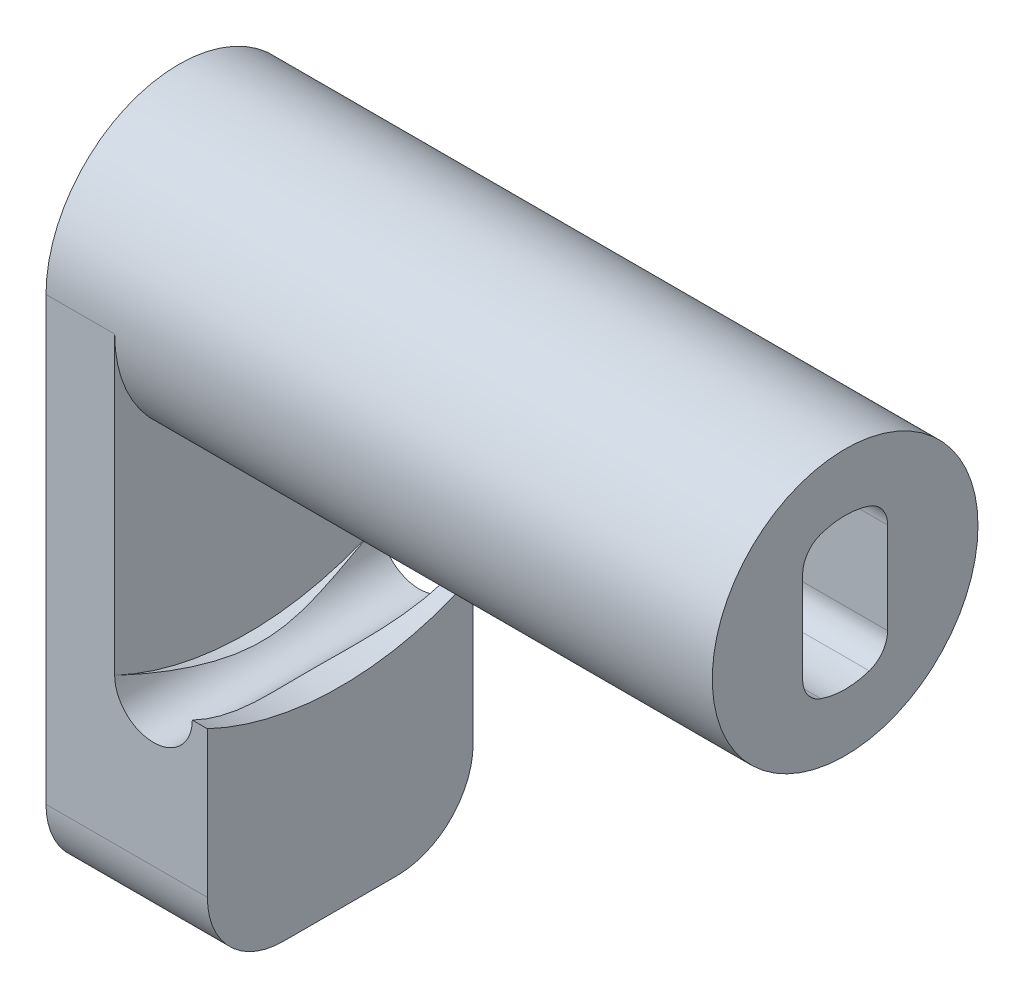
SolidWorks part; units mm, degrees
material "ABS"
ref_plane "Front Plane" through (0, 0, 0) normal (1, 0, 0) x (0, 1, 0)
ref_plane "Top Plane" through (0, 0, 0) normal (0, 0, 1) x (0, 1, 0)
ref_plane "Right Plane" through (0, 0, 0) normal (0, 1, 0) x (-1, 0, 0)
sketch "Sketch1" plane through (0, 0, 0) normal (1, 0, 0) x (0, 1, 0)
  circle A2 centre (0, 0) radius 8.7376
  dimension "D3" = 17.4752
extrude "Boss-Extrude1" add sketch "Sketch1" along normal blind 43.815 contours A2 region at (0, 0, 0)
sketch "Sketch10" plane through (0, 0, 0) normal (-1, 0, 0) x (0, -1, 0)
  line L0 (0, 8.7376) -> (34.036, 8.7376)
  line L2 (34.036, 8.7376) -> (34.036, -8.7376)
  line L3 (34.036, -8.7376) -> (0, -8.7376)
  circle A0 centre (0, 0) radius 8.7376 construction
  arc A2 (0, 8.7376) -> (0, -8.7376) centre (0, 0) cw
  dimension "D1" = 34.036
extrude "Boss-Extrude3" add sketch "Sketch10" against normal blind 4.516 contours L0 A2 L3 L2 region at (0, -20.3793, 0)
fillet "Fillet2" radius 5 2 edges at (2.258, -34.036, 8.7376) (2.258, -34.036, -8.7376)
sketch "Sketch14" [suppressed] plane through (0, 0, 0) normal (-1, 0, 0) x (0, 0, 1)
  line L0 (0.5115, -3.4237) -> (0.3944, -4.0089)
  line L1 (0, 0) -> (0, -4.064) construction
  line L2 (0, 0) -> (0.5606, -3.4335) construction
  line L3 (0.6039, -3.4087) -> (0.9011, -3.9262)
  line L4 (-0.6903, -3.3922) -> (-1.0005, -3.9021)
  line L5 (-0.5983, -3.4096) -> (-0.4961, -3.9976)
  line L6 (-1.8089, -2.9515) -> (-2.2748, -3.3245)
  line L7 (-1.7284, -2.9994) -> (-1.8334, -3.5869)
  line L8 (-2.7093, -2.1549) -> (-3.2746, -2.346)
  line L9 (-2.65, -2.2273) -> (-2.9496, -2.7435)
  line L10 (-3.2829, -1.0983) -> (-3.8795, -1.0846)
  line L11 (-3.252, -1.1867) -> (-3.7101, -1.5692)
  line L12 (-3.4605, 0.0907) -> (-4.0165, 0.3077)
  line L13 (-3.4617, -0.0029) -> (-4.023, -0.2057)
  line L14 (-3.2208, 1.2689) -> (-3.669, 1.6629)
  line L15 (-3.2539, 1.1813) -> (-3.8507, 1.1827)
  line L16 (-2.5926, 2.2939) -> (-2.879, 2.8175)
  line L17 (-2.6537, 2.223) -> (-3.214, 2.4284)
  line L18 (-1.6517, 3.0423) -> (-1.7417, 3.6323)
  line L19 (-1.7333, 2.9965) -> (-2.1896, 3.3812)
  line L20 (-0.5115, 3.4237) -> (-0.3944, 4.0089)
  line L21 (-0.6039, 3.4087) -> (-0.9011, 3.9262)
  line L22 (0.6903, 3.3922) -> (1.0005, 3.9021)
  line L23 (0.5983, 3.4096) -> (0.4961, 3.9976)
  line L24 (1.8089, 2.9515) -> (2.2748, 3.3245)
  line L25 (1.7284, 2.9994) -> (1.8334, 3.5869)
  line L26 (2.7093, 2.1549) -> (3.2746, 2.346)
  line L27 (2.65, 2.2273) -> (2.9496, 2.7435)
  line L28 (3.2829, 1.0983) -> (3.8795, 1.0846)
  line L29 (3.252, 1.1867) -> (3.7101, 1.5692)
  line L30 (3.4605, -0.0907) -> (4.0165, -0.3077)
  line L31 (3.4617, 0.0029) -> (4.023, 0.2057)
  line L32 (3.2208, -1.2689) -> (3.669, -1.6629)
  line L33 (3.2539, -1.1813) -> (3.8507, -1.1827)
  line L34 (2.5926, -2.2939) -> (2.879, -2.8175)
  line L35 (2.6537, -2.223) -> (3.214, -2.4284)
  line L36 (1.6517, -3.0423) -> (1.7417, -3.6323)
  line L37 (1.7333, -2.9965) -> (2.1896, -3.3812)
  line L38 (-0.1032, -4.0627) -> (0, -4.064)
  line L39 (-1.4865, -3.7824) -> (-1.39, -3.8189)
  line L40 (-2.6905, -3.0459) -> (-2.6123, -3.1132)
  line L41 (-3.5195, -2.032) -> (-3.57, -1.942)
  line L42 (-4.0023, -0.7057) -> (-4.0189, -0.6039)
  line L43 (-4.0023, 0.7057) -> (-3.9831, 0.8071)
  line L44 (-3.5195, 2.032) -> (-3.4668, 2.1207)
  line L45 (-2.6123, 3.1132) -> (-2.5324, 3.1785)
  line L46 (-1.39, 3.8189) -> (-1.2926, 3.853)
  line L47 (0, 4.064) -> (0.1032, 4.0627)
  line L48 (1.39, 3.8189) -> (1.4865, 3.7824)
  line L49 (2.6123, 3.1132) -> (2.6905, 3.0459)
  line L50 (3.5195, 2.032) -> (3.57, 1.942)
  line L51 (4.0023, 0.7057) -> (4.0189, 0.6039)
  line L52 (4.0023, -0.7057) -> (3.9831, -0.8071)
  line L53 (3.5195, -2.032) -> (3.4668, -2.1207)
  line L54 (2.6123, -3.1132) -> (2.5324, -3.1785)
  line L55 (1.39, -3.8189) -> (1.2926, -3.853)
  arc A0 (0.3497, -4.0489) -> (0, -4.064) centre (0, 0) cw
  arc A1 (0.3497, -4.0489) -> (0.3944, -4.0089) centre (0.3454, -3.9991) ccw
  arc A2 (0.5115, -3.4237) -> (0.6039, -3.4087) centre (0.5606, -3.4335) cw
  arc A3 (0.4203, -4.0631) -> (0.3944, -4.0089) centre (0.4434, -4.0187) cw
  arc A4 (0.4203, -4.0631) -> (0.7372, -4.2116) centre (2.3016, -0.4608) ccw
  arc A6 (0.9562, -3.9499) -> (0.9011, -3.9262) centre (0.9445, -3.9013) cw
  arc A7 (0.9562, -3.9499) -> (1.2926, -3.853) centre (0, 0) ccw
  arc A8 (-1.0562, -3.9243) -> (-1.39, -3.8189) centre (0, 0) cw
  arc A9 (-1.0562, -3.9243) -> (-1.0005, -3.9021) centre (-1.0432, -3.8761) ccw
  arc A10 (-0.6903, -3.3922) -> (-0.5983, -3.4096) centre (-0.6476, -3.4182) cw
  arc A11 (-0.4524, -4.0387) -> (-0.4961, -3.9976) centre (-0.4468, -3.9891) cw
  arc A12 (-0.4524, -4.0387) -> (-0.1032, -4.0627) centre (0, 0) ccw
  arc A13 (-2.3347, -3.3264) -> (-2.6123, -3.1132) centre (0, 0) cw
  arc A14 (-2.3347, -3.3264) -> (-2.2748, -3.3245) centre (-2.306, -3.2855) ccw
  arc A15 (-1.8089, -2.9515) -> (-1.7284, -2.9994) centre (-1.7776, -2.9906) cw
  arc A16 (-1.8064, -3.6405) -> (-1.8334, -3.5869) centre (-1.7842, -3.5957) cw
  arc A17 (-1.8064, -3.6405) -> (-1.4865, -3.7824) centre (0, 0) ccw
  arc A18 (-3.3316, -2.3273) -> (-3.5195, -2.032) centre (0, 0) cw
  arc A19 (-3.3316, -2.3273) -> (-3.2746, -2.346) centre (-3.2906, -2.2987) ccw
  arc A20 (-2.7093, -2.1549) -> (-2.65, -2.2273) centre (-2.6933, -2.2022) cw
  arc A21 (-2.9426, -2.8031) -> (-2.9496, -2.7435) centre (-2.9064, -2.7686) cw
  arc A22 (-2.9426, -2.8031) -> (-2.6905, -3.0459) centre (0, 0) ccw
  arc A23 (-3.9267, -1.0475) -> (-4.0023, -0.7057) centre (0, 0) cw
  arc A24 (-3.9267, -1.0475) -> (-3.8795, -1.0846) centre (-3.8784, -1.0346) ccw
  arc A25 (-3.2829, -1.0983) -> (-3.252, -1.1867) centre (-3.284, -1.1483) cw
  arc A26 (-3.7238, -1.6276) -> (-3.7101, -1.5692) centre (-3.678, -1.6076) cw
  arc A27 (-3.7238, -1.6276) -> (-3.57, -1.942) centre (0, 0) ccw
  arc A28 (-4.0481, 0.3587) -> (-4.0023, 0.7057) centre (0, 0) cw
  arc A29 (-4.0481, 0.3587) -> (-4.0165, 0.3077) centre (-3.9983, 0.3543) ccw
  arc A30 (-3.4605, 0.0907) -> (-3.4617, -0.0029) centre (-3.4787, 0.0442) cw
  arc A31 (-4.0559, -0.2558) -> (-4.023, -0.2057) centre (-4.006, -0.2527) cw
  arc A32 (-4.0559, -0.2558) -> (-4.0189, -0.6039) centre (0, 0) ccw
  arc A33 (-3.6813, 1.7216) -> (-3.5195, 2.032) centre (0, 0) cw
  arc A34 (-3.6813, 1.7216) -> (-3.669, 1.6629) centre (-3.636, 1.7005) ccw
  arc A35 (-3.2208, 1.2689) -> (-3.2539, 1.1813) centre (-3.2538, 1.2313) cw
  arc A36 (-3.8988, 1.1468) -> (-3.8507, 1.1827) centre (-3.8509, 1.1327) cw
  arc A37 (-3.8988, 1.1468) -> (-3.9831, 0.8071) centre (0, 0) ccw
  arc A38 (-2.8705, 2.8769) -> (-2.6123, 3.1132) centre (0, 0) cw
  arc A39 (-2.8705, 2.8769) -> (-2.879, 2.8175) centre (-2.8352, 2.8415) ccw
  arc A40 (-2.5926, 2.2939) -> (-2.6537, 2.223) centre (-2.6365, 2.2699) cw
  arc A41 (-3.2715, 2.4111) -> (-3.214, 2.4284) centre (-3.2312, 2.3815) cw
  arc A42 (-3.2715, 2.4111) -> (-3.4668, 2.1207) centre (0, 0) ccw
  arc A43 (-1.7134, 3.6852) -> (-1.39, 3.8189) centre (0, 0) cw
  arc A44 (-1.7134, 3.6852) -> (-1.7417, 3.6323) centre (-1.6923, 3.6398) ccw
  arc A45 (-1.6517, 3.0423) -> (-1.7333, 2.9965) centre (-1.7011, 3.0348) cw
  arc A46 (-2.2495, 3.3846) -> (-2.1896, 3.3812) centre (-2.2218, 3.343) cw
  arc A47 (-2.2495, 3.3846) -> (-2.5324, 3.1785) centre (0, 0) ccw
  arc A48 (-0.3497, 4.0489) -> (0, 4.064) centre (0, 0) cw
  arc A49 (-0.3497, 4.0489) -> (-0.3944, 4.0089) centre (-0.3454, 3.9991) ccw
  arc A50 (-0.5115, 3.4237) -> (-0.6039, 3.4087) centre (-0.5606, 3.4335) cw
  arc A51 (-0.9562, 3.9499) -> (-0.9011, 3.9262) centre (-0.9445, 3.9013) cw
  arc A52 (-0.9562, 3.9499) -> (-1.2926, 3.853) centre (0, 0) ccw
  arc A53 (1.0562, 3.9243) -> (1.39, 3.8189) centre (0, 0) cw
  arc A54 (1.0562, 3.9243) -> (1.0005, 3.9021) centre (1.0432, 3.8761) ccw
  arc A55 (0.6903, 3.3922) -> (0.5983, 3.4096) centre (0.6476, 3.4182) cw
  arc A56 (0.4524, 4.0387) -> (0.4961, 3.9976) centre (0.4468, 3.9891) cw
  arc A57 (0.4524, 4.0387) -> (0.1032, 4.0627) centre (0, 0) ccw
  arc A58 (2.3347, 3.3264) -> (2.6123, 3.1132) centre (0, 0) cw
  arc A59 (2.3347, 3.3264) -> (2.2748, 3.3245) centre (2.306, 3.2855) ccw
  arc A60 (1.8089, 2.9515) -> (1.7284, 2.9994) centre (1.7776, 2.9906) cw
  arc A61 (1.8064, 3.6405) -> (1.8334, 3.5869) centre (1.7842, 3.5957) cw
  arc A62 (1.8064, 3.6405) -> (1.4865, 3.7824) centre (0, 0) ccw
  arc A63 (3.3316, 2.3273) -> (3.5195, 2.032) centre (0, 0) cw
  arc A64 (3.3316, 2.3273) -> (3.2746, 2.346) centre (3.2906, 2.2987) ccw
  arc A65 (2.7093, 2.1549) -> (2.65, 2.2273) centre (2.6933, 2.2022) cw
  arc A66 (2.9426, 2.8031) -> (2.9496, 2.7435) centre (2.9064, 2.7686) cw
  arc A67 (2.9426, 2.8031) -> (2.6905, 3.0459) centre (0, 0) ccw
  arc A68 (3.9267, 1.0475) -> (4.0023, 0.7057) centre (0, 0) cw
  arc A69 (3.9267, 1.0475) -> (3.8795, 1.0846) centre (3.8784, 1.0346) ccw
  arc A70 (3.2829, 1.0983) -> (3.252, 1.1867) centre (3.284, 1.1483) cw
  arc A71 (3.7238, 1.6276) -> (3.7101, 1.5692) centre (3.678, 1.6076) cw
  arc A72 (3.7238, 1.6276) -> (3.57, 1.942) centre (0, 0) ccw
  arc A73 (4.0481, -0.3587) -> (4.0023, -0.7057) centre (0, 0) cw
  arc A74 (4.0481, -0.3587) -> (4.0165, -0.3077) centre (3.9983, -0.3543) ccw
  arc A75 (3.4605, -0.0907) -> (3.4617, 0.0029) centre (3.4787, -0.0442) cw
  arc A76 (4.0559, 0.2558) -> (4.023, 0.2057) centre (4.006, 0.2527) cw
  arc A77 (4.0559, 0.2558) -> (4.0189, 0.6039) centre (0, 0) ccw
  arc A78 (3.6813, -1.7216) -> (3.5195, -2.032) centre (0, 0) cw
  arc A79 (3.6813, -1.7216) -> (3.669, -1.6629) centre (3.636, -1.7005) ccw
  arc A80 (3.2208, -1.2689) -> (3.2539, -1.1813) centre (3.2538, -1.2313) cw
  arc A81 (3.8988, -1.1468) -> (3.8507, -1.1827) centre (3.8509, -1.1327) cw
  arc A82 (3.8988, -1.1468) -> (3.9831, -0.8071) centre (0, 0) ccw
  arc A83 (2.8705, -2.8769) -> (2.6123, -3.1132) centre (0, 0) cw
  arc A84 (2.8705, -2.8769) -> (2.879, -2.8175) centre (2.8352, -2.8415) ccw
  arc A85 (2.5926, -2.2939) -> (2.6537, -2.223) centre (2.6365, -2.2699) cw
  arc A86 (3.2715, -2.4111) -> (3.214, -2.4284) centre (3.2312, -2.3815) cw
  arc A87 (3.2715, -2.4111) -> (3.4668, -2.1207) centre (0, 0) ccw
  arc A88 (1.7134, -3.6852) -> (1.39, -3.8189) centre (0, 0) cw
  arc A89 (1.7134, -3.6852) -> (1.7417, -3.6323) centre (1.6923, -3.6398) ccw
  arc A90 (1.6517, -3.0423) -> (1.7333, -2.9965) centre (1.7011, -3.0348) cw
  arc A91 (2.2495, -3.3846) -> (2.1896, -3.3812) centre (2.2218, -3.343) cw
  arc A92 (2.2495, -3.3846) -> (2.5324, -3.1785) centre (0, 0) ccw
  point P207 (0, 0)
  dimension "D1" = 4.064
  dimension "D2" = 0.05
  dimension "D3" = 0.05
  dimension "D4" = 0.04
  dimension "D5" = 18
  dimension "D6" = 0.5968
  dimension "D8" = 0.35
sketch "Sketch15" plane through (4.516, 0, 0) normal (1, 0, 0) x (0, 1, 0)
  line L1 (-29.036, 8.7376) -> (-18.796, 8.7376)
  line L2 (-18.796, 8.7376) -> (-18.796, -8.7376)
  line L3 (0, 8.7376) -> (-29.036, 8.7376) construction
  line L4 (-29.036, -8.7376) -> (-18.796, -8.7376)
  line L5 (-34.036, 3.7376) -> (-34.036, -3.7376) construction
  line L6 (-34.036, 3.7376) -> (-34.036, -3.7376)
  line L8 (-29.036, -8.7376) -> (0, -8.7376) construction
  line L13 (0, 8.7376) -> (-29.036, 8.7376)
  line L14 (-34.036, 3.7376) -> (-34.036, -3.7376)
  line L15 (-29.036, -8.7376) -> (0, -8.7376)
  line L17 (-34.036, 3.7376) -> (-34.036, -3.7376)
  arc A0 (-29.036, 8.7376) -> (-34.036, 3.7376) centre (-29.036, 3.7376) ccw construction
  arc A1 (-34.036, -3.7376) -> (-29.036, -8.7376) centre (-29.036, -3.7376) ccw construction
  arc A2 (-29.036, 8.7376) -> (-34.036, 3.7376) centre (-29.036, 3.7376) ccw
  arc A3 (-34.036, -3.7376) -> (-29.036, -8.7376) centre (-29.036, -3.7376) ccw
  arc A7 (-29.036, 8.7376) -> (-34.036, 3.7376) centre (-29.036, 3.7376) ccw
  arc A8 (-34.036, -3.7376) -> (-29.036, -8.7376) centre (-29.036, -3.7376) ccw
  arc A9 (0, 8.7376) -> (0, -8.7376) centre (0, 0) ccw
  arc A10 (-29.036, 8.7376) -> (-34.036, 3.7376) centre (-29.036, 3.7376) ccw
  arc A11 (-34.036, -3.7376) -> (-29.036, -8.7376) centre (-29.036, -3.7376) ccw
  arc A12 (0, 8.7376) -> (0, -8.7376) centre (0, 0) ccw
  line M2 (0, 8.7376) -> (-29.036, 8.7376)
  arc M3 (-29.036, 8.7376) -> (-34.036, 3.7376) centre (-29.036, 3.7376) ccw
  line M4 (-34.036, 3.7376) -> (-34.036, -3.7376)
  arc M5 (-34.036, -3.7376) -> (-29.036, -8.7376) centre (-29.036, -3.7376) ccw
  dimension "D1" = 15.24
  dimension "D2" = 0
extrude "Boss-Extrude4" add sketch "Sketch15" along normal blind 6.096 contours M2 M3 M4 M5 region at (4.516, -26.143, 0)
sketch "Sketch21" plane through (10.612, 0, 0) normal (1, 0, 0) x (0, 1, 0)
  line L2 (-18.796, -8.7376) -> (-18.796, 8.7376)
  line L4 (-29.036, 8.7376) -> (-18.796, 8.7376) construction
  line L5 (-19.431, -8.7376) -> (-18.796, -8.7376)
  line L6 (-18.796, 8.7376) -> (-18.796, -8.7376) construction
  line L8 (-18.796, -8.7376) -> (0, -8.7376) construction
  line L14 (-18.796, -8.7376) -> (-18.796, 8.7376) construction
  line L20 (-18.796, 8.7376) -> (-29.036, 8.7376)
  arc A2 (-19.431, -8.7376) -> (-19.431, 8.7376) centre (-1.0855, 0) cw
  dimension "D4" = 20.32
  dimension "D2" = 0.635
  dimension "D3" = 0.635
extrude "Cut-Extrude8" cut sketch "Sketch21" against normal up to surface (6.096 mm away) contours A2 L2 region at (10.612, -19.8652, 0) up to face at (4.516, -11.5824, 0)
sketch "Sketch22" plane through (43.815, 0, 0) normal (1, 0, 0) x (0, 1, 0)
  line L7 (-4.0897, -2.794) -> (4.0897, 2.794) construction
  line L8 (-4.0897, 2.794) -> (4.0897, -2.794) construction
  line L11 (-4.0897, -2.794) -> (4.0897, -2.794)
  line L13 (-4.0897, 2.794) -> (4.0897, 2.794)
  line L15 (-4.0897, -2.794) -> (4.0897, 2.794) construction
  line L16 (-4.0897, 2.794) -> (4.0897, -2.794) construction
  arc A3 (-4.0897, 2.794) -> (-4.0897, -2.794) centre (0, 0) ccw
  arc A4 (4.0897, -2.794) -> (4.0897, 2.794) centre (0, 0) ccw
  dimension "D2" = 9.906
  dimension "D3" = 5.588
extrude "Cut-Extrude10" cut sketch "Sketch22" against normal blind 12.192
fillet "Fillet11" radius 1.778 4 edges at (37.719, 4.0897, -2.794) (37.719, 4.0897, 2.794) (37.719, -4.0897, -2.794) (37.719, -4.0897, 2.794)
sketch "Sketch25" plane through (0, 0, -8.7376) normal (0, 0, -1) x (1, 0, 0)
  line L3 (4.516, 19.431) -> (4.516, 0) construction
  line L4 (4.516, 19.431) -> (10.612, 19.431) construction
  circle A0 centre (7.0687, 19.431) radius 2.5527
  dimension "D1" = 5.1054
extrude "Cut-Extrude14" cut sketch "Sketch25" against normal through all
sketch "Sketch26" plane through (0, 0, 0) normal (-1, 0, 0) x (0, -1, 0)
  line L1 (3.6846, 1.7145) -> (7.1771, 1.7145)
  line L2 (3.6846, 1.7145) -> (3.6846, -1.7145) construction
  line L3 (3.6846, -1.7145) -> (7.1771, -1.7145)
  line L4 (7.1771, 1.7145) -> (7.1771, -1.7145)
  arc A0 (3.6846, 1.7145) -> (3.6846, -1.7145) centre (0, 0) ccw
  dimension "D1" = 8.128
  dimension "D2" = 3.429
  dimension "D3" = 3.4925
extrude "Cut-Extrude15" cut sketch "Sketch26" against normal blind 21.59
fillet "Fillet12" radius 1.5875 4 edges at (10.795, -3.6846, 1.7145) (10.795, -7.1771, 1.7145) (10.795, -3.6846, -1.7145) (10.795, -7.1771, -1.7145)
